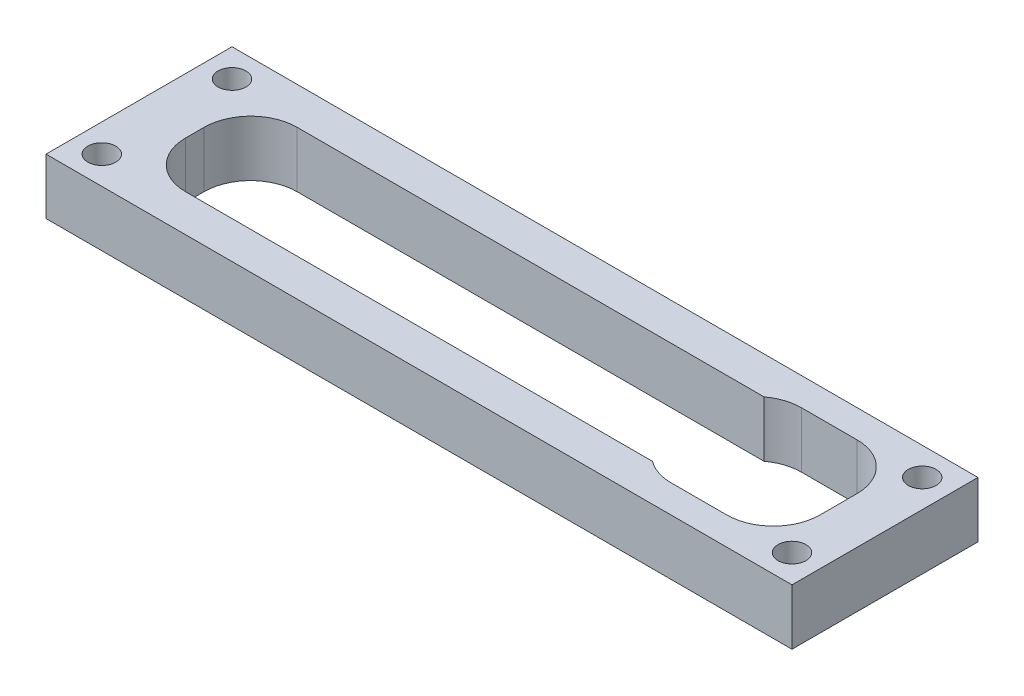
SolidWorks part; units mm, degrees
ref_plane "Front Plane" through (0, 0, 0) normal (0, 0, 1) x (1, 0, 0)
ref_plane "Top Plane" through (0, 0, 0) normal (0, 1, 0) x (1, 0, 0)
ref_plane "Right Plane" through (0, 0, 0) normal (1, 0, 0) x (0, 0, -1)
sketch "Sketch1" plane through (0, 0, 0) normal (0, 1, 0) x (1, 0, 0)
  line L0 (40.107, 20) -> (40.107, 0) construction
  line L1 (0, 0) -> (80.2139, 0)
  line L2 (0, 0) -> (0, 20)
  line L3 (0, 20) -> (80.2139, 20)
  line L4 (80.2139, 0) -> (80.2139, 20)
  line L5 (0, 10) -> (80.2139, 10) construction
  line L6 (40.107, 16) -> (40.107, 4) construction
  line L7 (6, 16) -> (74.2139, 16)
  line L8 (6, 16) -> (6, 4)
  line L9 (6, 4) -> (74.2139, 4)
  line L10 (74.2139, 16) -> (74.2139, 4)
  line L11 (6, 10) -> (74.2139, 10) construction
  circle A0 centre (3, 17) radius 1.5
  circle A1 centre (3, 3) radius 1.5
  circle A2 centre (77.2139, 3) radius 1.5
  circle A3 centre (77.2139, 17) radius 1.5
  point P17 (40.107, 10)
  point P18 (40.107, 10)
  dimension "D7" = 3
  dimension "D1" = 80.2139
  dimension "D2" = 20
  dimension "D3" = 68.2139
  dimension "D4" = 12
  dimension "D5" = 3
  dimension "D6" = 3
extrude "Boss-Extrude1" add sketch "Sketch1" along normal blind 6
sketch "Sketch2" plane through (0, 6, 0) normal (0, 1, 0) x (1, 0, 0)
  line L0 (92, 10) -> (-49908, 10) construction
  line L1 (74.2139, 4) -> (74.2139, 16) construction
  line L2 (61.2139, 17) -> (61.2139, 16)
  line L5 (74.2139, 16) -> (6, 16) construction
  line L6 (68.2139, 17) -> (68.2139, 3) construction
  line L7 (61.2139, 17) -> (75.2139, 17)
  line L9 (61.2139, 3) -> (75.2139, 3)
  line L10 (75.2139, 17) -> (75.2139, 3)
  line L12 (61.2139, 16) -> (74.2139, 16)
  line L13 (74.2139, 16) -> (74.2139, 4)
  line L14 (74.2139, 4) -> (61.2139, 4)
  line L15 (6, 4) -> (74.2139, 4) construction
  line L16 (61.2139, 4) -> (61.2139, 3)
  point P4 (74.2139, 10)
  point P23 (68.2139, 10)
  dimension "D1" = 1
  dimension "D2" = 14
  dimension "D3" = 14
extrude "Cut-Extrude1" cut sketch "Sketch2" against normal through all
fillet "Fillet1" radius 5 6 edges at (75.2139, 3, -17) (75.2139, 3, -3) (61.2139, 3, -17) (61.2139, 3, -3) (6, 3, -4) (6, 3, -16)
equation "\"TrackLength\"= ( ( \"n\" * 28 ) ) / cos ( \"MountAngle\" ) - ( 2 * \"x\" )"
equation "\"D1@Sketch1\"=\"TrackLength\""
equation "\"TrackWidth\"= \"MarbleTrackWidth\" + ( 2 * 4 )"
equation "\"D2@Sketch1\"=\"TrackWidth\""
equation "\"MarbleTrackWidth\"= \"MarbleWidth\" - 1"
equation "\"MarbleTrackLength\"= \"TrackLength\" - ( 2 * 6 )"
equation "\"D3@Sketch1\"=\"MarbleTrackLength\""
equation "\"D4@Sketch1\"=\"MarbleTrackWidth\""
equation "\"MarbleWidth\"= 13"
equation "\"n\"= 3"
equation "\"MountAngle\" = 5"
equation "\"x\"= 14 / cos ( \"MountAngle\" ) - 12"
